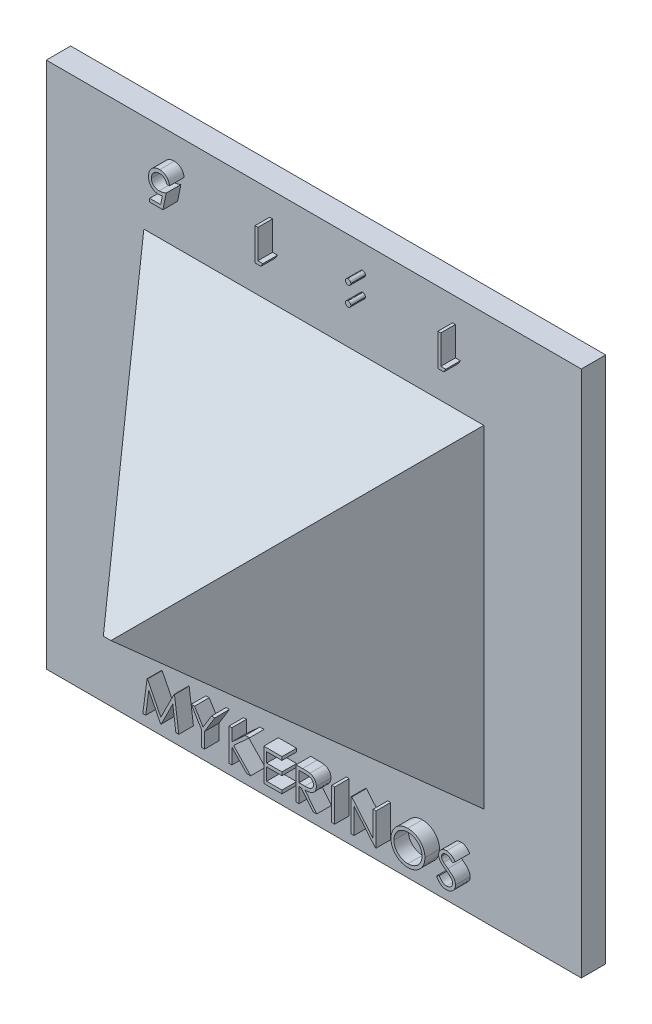
SolidWorks part; units mm, degrees
ref_plane "Plan de face" through (0, 0, 0) normal (0, 0, 1) x (1, 0, 0)
ref_plane "Plan de dessus" through (0, 0, 0) normal (0, 1, 0) x (1, 0, 0)
ref_plane "Plan de droite" through (0, 0, 0) normal (1, 0, 0) x (0, 0, -1)
sketch "Esquisse1" plane through (0, 0, 0) normal (0, 0, 1) x (1, 0, 0)
  line L1 (0, 0) -> (69.7, 0)
  line L2 (0, 0) -> (0, 68.13)
  line L3 (0, 68.13) -> (69.7, 68.13)
  line L4 (69.7, 0) -> (69.7, 68.13)
  dimension "D1" = 69.7
  dimension "D2" = 68.13
extrude "Boss.-Extru.1" add sketch "Esquisse1" along normal blind 50 draft 38.8
sketch "Esquisse3" plane through (0, 0, 0) normal (0, 0, -1) x (-1, 0, 0)
  line L8 (20, -20) -> (20, 88.13)
  line L9 (20, 88.13) -> (-89.7, 88.13)
  line L10 (-89.7, 88.13) -> (-89.7, -20)
  line L11 (-89.7, -20) -> (20, -20)
  line L12 (20, -20) -> (20, 88.13)
  line L13 (20, 88.13) -> (-89.7, 88.13)
  line L14 (-89.7, 88.13) -> (-89.7, -20)
  line L15 (-89.7, -20) -> (20, -20)
  dimension "D1" = 20
extrude "Boss.-Extru.3" add sketch "Esquisse3" along normal blind 5 separate body
sketch "Esquisse2" plane through (0, 0, -5) normal (0, 0, -1) x (-1, 0, 0)
  line L0 (0, 0) -> (-69.7, 0) construction
  line L1 (0, 68.13) -> (0, 0) construction
  circle A0 centre (-34.85, 34.065) radius 23.25
  point P5 (-34.85, 0)
  point P8 (0, 34.065)
  dimension "D1" = 46.5
extrude "Boss.-Extru.2" [suppressed] add sketch "Esquisse2" along normal blind 30
sketch "Esquisse4" plane through (0, 0, 0) normal (0, 0, 1) x (1, 0, 0)
  line L0 (2.2826, -15) -> (67.4174, -15) construction
  line L1 (3.5262, 83.13) -> (66.1738, 83.13) construction
  line L2 (0, 0) -> (69.7, 0) construction
  line L3 (89.7, -20) -> (-20, -20) construction
  line L4 (69.7, 68.13) -> (0, 68.13) construction
  line L5 (-20, 88.13) -> (89.7, 88.13) construction
  text T0 "MYKERINOS" font "Century Gothic" height in points 25
  text T1 "1:15" font "Century Gothic" height in points 25
  point P6 (34.85, 0)
  point P7 (34.85, -15)
  point P12 (34.85, 68.13)
  point P13 (34.85, 83.13)
  dimension "D1" = 5
  dimension "D2" = 5
extrude "Boss.-Extru.4" add sketch "Esquisse4" along normal blind 3
